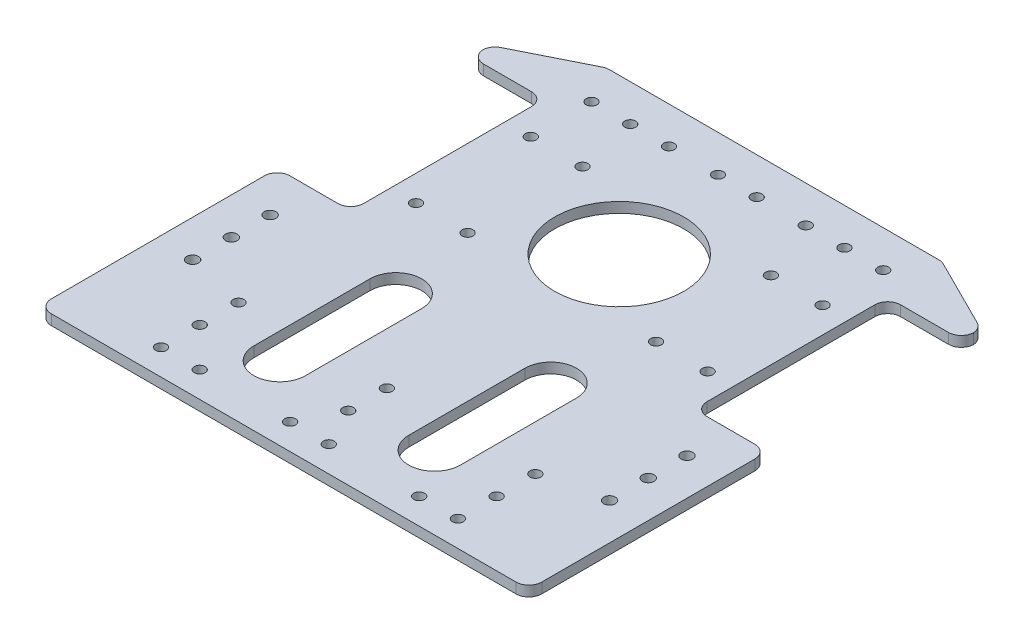
SolidWorks part; units mm, degrees
ref_plane "Alzado" through (0, 0, 0) normal (0, 0, 1) x (1, 0, 0)
ref_plane "Planta" through (0, 0, 0) normal (0, 1, 0) x (1, 0, 0)
ref_plane "Vista lateral" through (0, 0, 0) normal (1, 0, 0) x (0, 0, -1)
sketch "Croquis1" plane through (0, 0, 0) normal (0, 1, 0) x (1, 0, 0)
  line L0 (-97.5, 35) -> (97.5, 35) construction
  line L1 (-95, 95) -> (95, 95)
  line L2 (-95, 95) -> (-95, -95)
  line L3 (-95, -95) -> (95, -95)
  line L4 (95, 95) -> (95, -95)
  line L5 (0, -95) -> (0, 95) construction
  line L6 (-95, 0) -> (95, 0) construction
  line L8 (71.5, 67.5) -> (97.5, 67.5)
  line L9 (71.5, 67.5) -> (71.5, 2.5)
  line L10 (71.5, 2.5) -> (97.5, 2.5)
  line L11 (97.5, 67.5) -> (97.5, 2.5)
  line L12 (84.5, 2.5) -> (84.5, 67.5) construction
  line L13 (71.5, 35) -> (97.5, 35) construction
  line L18 (-64, 47.2) -> (-64, 22.8)
  line L19 (-64, 47.2) -> (-61, 47.2)
  line L22 (-95, 95) -> (-95, 22.8)
  line L23 (-71.5, 2.5) -> (-97.5, 2.5)
  line L24 (-71.5, 67.5) -> (-97.5, 67.5)
  line L25 (-71.5, 67.5) -> (-71.5, 2.5)
  line L26 (-84.5, 2.5) -> (-84.5, 67.5) construction
  line L27 (-97.5, 67.5) -> (-97.5, 2.5)
  line L28 (-64, 22.8) -> (-61, 22.8)
  line L29 (-61, 47.2) -> (-61, 22.8)
  line L30 (-61, 22.8) -> (-61, 47.2)
  line L31 (-61, 22.8) -> (-5, 22.8)
  line L32 (95, 95) -> (95, 22.8)
  line L33 (-61, 47.2) -> (-5, 47.2)
  line L34 (-5, 22.8) -> (-5, 47.2)
  line L35 (95, 95) -> (95, 22.8)
  line L36 (64, 22.8) -> (61, 22.8)
  line L37 (61, 47.2) -> (5, 47.2)
  line L38 (5, 22.8) -> (5, 47.2)
  line L39 (61, 22.8) -> (5, 22.8)
  line L40 (61, 22.8) -> (61, 47.2)
  line L41 (61, 47.2) -> (61, 22.8)
  line L42 (64, 47.2) -> (61, 47.2)
  line L43 (64, 47.2) -> (64, 22.8)
  line L44 (64, 31.5) -> (71.5, 31.5)
  line L45 (-64, 38.5) -> (-71.5, 38.5)
  line L46 (-64, 38.5) -> (-64, 31.5)
  line L47 (-64, 31.5) -> (-71.5, 31.5)
  line L48 (-71.5, 38.5) -> (-71.5, 31.5)
  line L49 (-67.75, 31.5) -> (-67.75, 38.5) construction
  line L50 (-64, 35) -> (-71.5, 35) construction
  line L51 (64, 38.5) -> (71.5, 38.5)
  point P0 (0, 0)
  point P6 (0, 35)
  point P11 (-5, 35)
  point P25 (-84.5, 35)
  point P129 (84.5, 35)
  point P132 (-67.75, 35)
  dimension "D1" = 190
  dimension "D2" = 190
  dimension "D3" = 65
  dimension "D4" = 26
  dimension "D5" = 60
  dimension "D6" = 3
  dimension "D7" = 56
  dimension "D8" = 24.4
  dimension "D9" = 195
  dimension "D10" = 5
  dimension "D11" = 7
  dimension "D12" = 7
  dimension "D13" = 10
sketch "Croquis2" plane through (0, 0, 0) normal (0, 1, 0) x (1, 0, 0)
  line L0 (-95, 80) -> (-65, 95)
  line L1 (-95, 95) -> (95, 95)
  line L2 (-95, 95) -> (-95, -95)
  line L3 (-95, -95) -> (95, -95)
  line L4 (95, 95) -> (95, -95)
  line L5 (0, -95) -> (0, 95) construction
  line L6 (-95, 0) -> (95, 0) construction
  line L7 (95, 80) -> (65, 95)
  point P172 (0, 0)
  dimension "D1" = 15
  dimension "D2" = 30
extrude "Saliente-Extruir1" add sketch "Croquis2" along normal blind 4 contours L4 L7 L1 L0 L2 L3 region at (0, 0, 1.136)
sketch "Croquis3" plane through (0, 4, 0) normal (0, 1, 0) x (1, 0, 0)
  line L0 (-95, -2.5) -> (-66.5, -2.5)
  line L1 (-95, 95) -> (-95, -95) construction
  line L2 (-66.5, -2.5) -> (-66.5, 72.5)
  line L3 (-66.5, 72.5) -> (-95, 72.5)
  line L4 (-95, 72.5) -> (-95, -2.5)
  line L5 (-71.5, 2.5) -> (-97.5, 2.5) construction
  line L6 (-71.5, 67.5) -> (-97.5, 67.5) construction
  line L7 (-71.5, 67.5) -> (-71.5, 2.5) construction
  line L9 (95, 72.5) -> (95, -2.5)
  line L10 (0, -95) -> (0, 95)
  line L11 (0, -95) -> (0, 95) construction
  line L12 (66.5, 72.5) -> (95, 72.5)
  line L13 (66.5, -2.5) -> (66.5, 72.5)
  line L14 (95, -2.5) -> (66.5, -2.5)
  dimension "D1" = 5
  dimension "D2" = 5
  dimension "D3" = 5
  dimension "D4" = 0
extrude "Cortar-Extruir1" cut sketch "Croquis3" against normal through all
sketch "Croquis4" plane through (0, 4, 0) normal (0, 1, 0) x (1, 0, 0)
  line L0 (-80.75, -2.5) -> (-80.75, -95) construction
  line L1 (-95, -2.5) -> (-66.5, -2.5) construction
  line L2 (-95, -95) -> (95, -95) construction
  line L3 (0, 95) -> (0, -95) construction
  line L4 (-65, 95) -> (65, 95) construction
  line L5 (0, 80.75) -> (-66.5, 80.75) construction
  line L6 (-66.5, 72.5) -> (-66.5, 80.75) construction
  circle A0 centre (-80.75, -19.5) radius 2.25
  circle A1 centre (-80.75, -34.5) radius 2.25
  circle A2 centre (-80.75, -49.5) radius 2.25
  circle A4 centre (-56.5, 80.75) radius 2.1
  circle A5 centre (-41.5, 80.75) radius 2.1
  circle A6 centre (-26.5, 80.75) radius 2.1
  circle A8 centre (80.75, -49.5) radius 2.25
  circle A9 centre (80.75, -34.5) radius 2.25
  circle A10 centre (80.75, -19.5) radius 2.25
  circle A11 centre (26.5, 80.75) radius 2.1
  circle A12 centre (41.5, 80.75) radius 2.1
  circle A13 centre (56.5, 80.75) radius 2.1
  dimension "D1" = 4.5
  dimension "D2" = 17
  dimension "D3" = 15
  dimension "D4" = 15
  dimension "D7" = 4.2
  dimension "D8" = 15
  dimension "D9" = 15
  dimension "D10" = 10
  dimension "D6" = 14.25
extrude "Cortar-Extruir2" cut sketch "Croquis4" against normal through all
sketch "Croquis5" plane through (0, 4, 0) normal (0, 1, 0) x (1, 0, 0)
  line L2 (-30, -21.5362) -> (-30, -66.5362) construction
  line L3 (0, -95) -> (0, 95)
  line L4 (0, -95) -> (0, 95) construction
  line L5 (-20, -21.5362) -> (-20, -66.5362)
  line L6 (-40, -21.5362) -> (-40, -66.5362)
  line L7 (30, -21.5362) -> (30, -66.5362) construction
  line L8 (20, -21.5362) -> (20, -66.5362)
  line L9 (40, -21.5362) -> (40, -66.5362)
  line L10 (-66.5, 35) -> (66.5, 35) construction
  line L11 (-66.5, -2.5) -> (-66.5, 72.5) construction
  line L12 (66.5, 72.5) -> (66.5, -2.5) construction
  arc A0 (-20, -21.5362) -> (-40, -21.5362) centre (-30, -21.5362) ccw
  arc A1 (-40, -66.5362) -> (-20, -66.5362) centre (-30, -66.5362) ccw
  arc A2 (20, -21.5362) -> (40, -21.5362) centre (30, -21.5362) cw
  arc A3 (40, -66.5362) -> (20, -66.5362) centre (30, -66.5362) cw
  circle A4 centre (0, 35) radius 25
  point P2 (-30, -44.0362)
  point P11 (30, -44.0362)
  dimension "D2" = 10
  dimension "D5" = 50
  dimension "D3" = 45
  dimension "D4" = 30
  dimension "D1" = 0
extrude "Cortar-Extruir3" cut sketch "Croquis5" against normal through all
fillet "Redondeo1" radius 5 14 edges at (-95, 2, 95) (-65, 2, -95) (-95, 2, -80) (-95, 2, -72.5) (-66.5, 2, -72.5) (-95, 2, 2.5) (-66.5, 2, 2.5) (65, 2, -95) (95, 2, -80) (95, 2, -72.5) (66.5, 2, -72.5) (66.5, 2, 2.5) (95, 2, 2.5) (95, 2, 95)
sketch "Croquis6" plane through (0, 4, 0) normal (0, 1, 0) x (1, 0, 0)
  line L0 (-95, -85) -> (95, -85) construction
  line L1 (-95, -7.5) -> (-95, -90) construction
  line L2 (95, -7.5) -> (95, -90) construction
  line L3 (-90, -95) -> (90, -95) construction
  line L4 (0, -85) -> (0, -12.8262) construction
  line L5 (-57.5, -85) -> (-42.5, -85) construction
  line L6 (57.5, -85) -> (42.5, -85) construction
  line L7 (-7.5, -85) -> (7.5, -85) construction
  circle A0 centre (-57.5, -85) radius 2.1
  circle A1 centre (-42.5, -85) radius 2.1
  circle A3 centre (42.5, -85) radius 2.1
  circle A4 centre (57.5, -85) radius 2.1
  circle A5 centre (-7.5, -85) radius 2.1
  circle A6 centre (7.5, -85) radius 2.1
  point P14 (-50, -85)
  point P21 (50, -85)
  point P25 (0, -85)
  dimension "D2" = 4.2
  dimension "D3" = 15
  dimension "D5" = 4.2
  dimension "D6" = 15
  dimension "D1" = 10
  dimension "D4" = 50
extrude "Cortar-Extruir4" cut sketch "Croquis6" against normal through all
sketch "Croquis7" plane through (0, 4, 0) normal (0, 1, 0) x (1, 0, 0)
  line L0 (-57.5, -85) -> (-57.5, -34.9785) construction
  line L1 (57.5, -85) -> (57.5, -14.9991) construction
  line L2 (0, 0) -> (0, -110.2274) construction
  line L3 (-57.5, -70) -> (0, -70) construction
  circle A0 centre (-57.5, -70) radius 2.1
  circle A1 centre (-57.5, -55) radius 2.1
  circle A2 centre (-57.5, -85) radius 2.1 construction
  circle A3 centre (57.5, -55) radius 2.1
  circle A4 centre (57.5, -70) radius 2.1
  circle A5 centre (0, -70) radius 2.1
  circle A6 centre (0, -55) radius 2.1
  dimension "D1" = 4.2
  dimension "D2" = 15
  dimension "D3" = 15
  dimension "D4" = 4.2
  dimension "D5" = 15
extrude "Cortar-Extruir5" cut sketch "Croquis7" against normal through all
sketch "Croquis8" plane through (0, 0, 0) normal (0, -1, 0) x (1, 0, 0)
  line L0 (6.5, -47.25) -> (110.4267, -47.25) construction
  line L1 (6.5, -22.75) -> (110.4267, -22.75) construction
  line L2 (66.5, -57.25) -> (25.1293, -57.25) construction
  line L3 (66.5, -67.5) -> (66.5, -2.5) construction
  line L4 (110.4267, -22.75) -> (110.4267, -47.25) construction
  line L5 (110.4267, -35) -> (137.3548, -35) construction
  line L6 (0, 0) -> (0, -71.3996) construction
  circle A0 centre (56.5, -57.25) radius 2.1
  circle A1 centre (36.5, -57.25) radius 2.1
  circle A2 centre (56.5, -12.75) radius 2.1
  circle A3 centre (36.5, -12.75) radius 2.1
  circle A4 centre (-36.5, -12.75) radius 2.1
  circle A5 centre (-56.5, -12.75) radius 2.1
  circle A6 centre (-36.5, -57.25) radius 2.1
  circle A7 centre (-56.5, -57.25) radius 2.1
  dimension "D1" = 4.2
  dimension "D3" = 20
  dimension "D2" = 10
  dimension "D4" = 10
extrude "Cortar-Extruir6" cut sketch "Croquis8" against normal up to next
sketch "Croquis9" plane through (0, 4, 0) normal (0, 1, 0) x (1, 0, 0)
  line L0 (-26.5, 80.75) -> (26.5, 80.75) construction
  line L1 (0, 80.75) -> (0, 119.6223) construction
  circle A0 centre (-7.5, 80.75) radius 2.1
  circle A1 centre (7.5, 80.75) radius 2.1
  dimension "D1" = 15
  dimension "D2" = 4.2
  dimension "D3" = 7.5
extrude "Cortar-Extruir7" cut sketch "Croquis9" against normal through all
